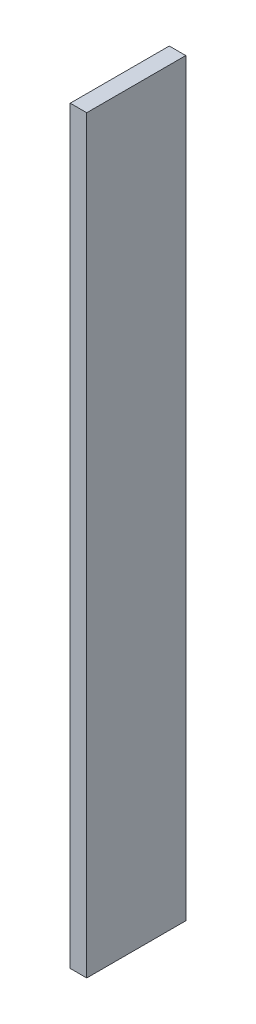
SolidWorks part; units mm, degrees
ref_plane "Спереди" through (0, 0, 0) normal (0, 0, 1) x (1, 0, 0)
ref_plane "Сверху" through (0, 0, 0) normal (0, 1, 0) x (1, 0, 0)
ref_plane "Справа" through (0, 0, 0) normal (1, 0, 0) x (0, 0, -1)
sketch "Эскиз1" plane through (0, 0, 0) normal (0, 1, 0) x (1, 0, 0)
  line L1 (0, 0) -> (5, 0)
  line L2 (0, 0) -> (0, -30)
  line L3 (0, -30) -> (5, -30)
  line L4 (5, 0) -> (5, -30)
  dimension "D1" = 5
  dimension "D2" = 30
extrude "Бобышка-Вытянуть1" add sketch "Эскиз1" along normal blind 227
